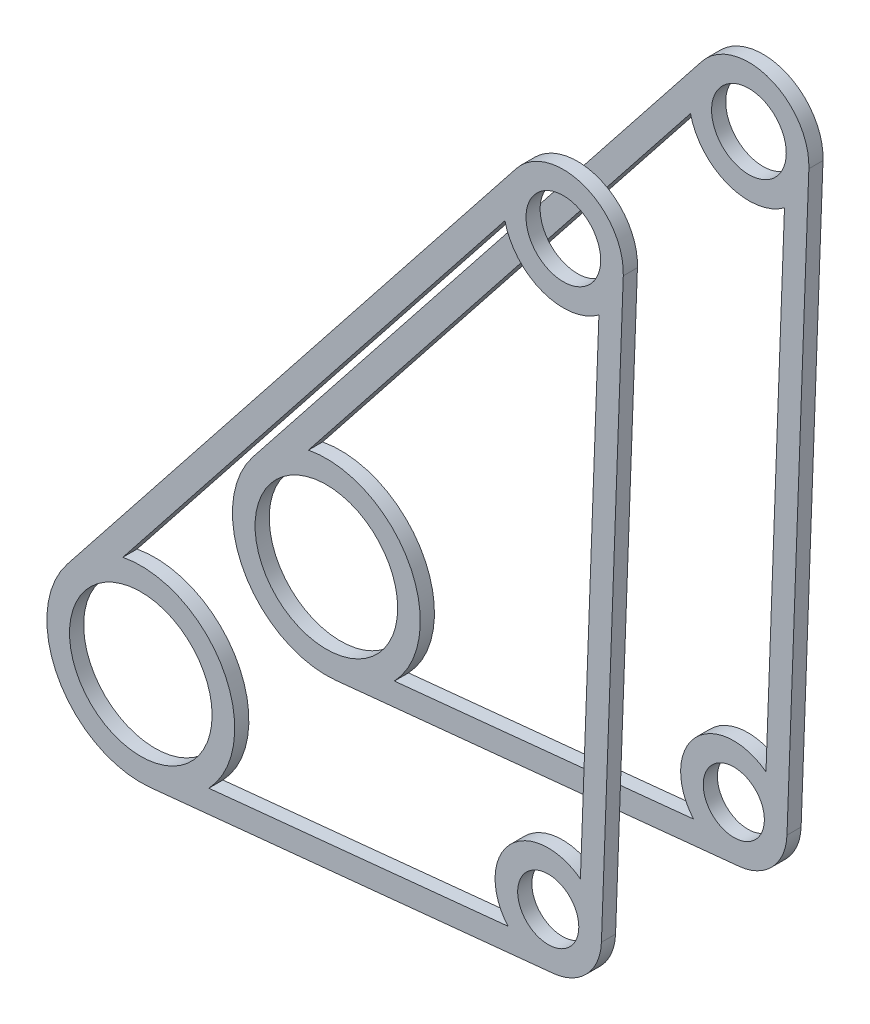
SolidWorks part; units mm, degrees
ref_plane "Front Plane" through (0, 0, 0) normal (0, 0, 1) x (1, 0, 0)
ref_plane "Top Plane" through (0, 0, 0) normal (0, 1, 0) x (1, 0, 0)
ref_plane "Right Plane" through (0, 0, 0) normal (1, 0, 0) x (0, 0, -1)
sketch "Sketch1" plane through (0, 0, 0) normal (0, 0, 1) x (1, 0, 0)
  line L0 (0, 0) -> (45.72, 0) construction
  line L1 (45.72, 0) -> (47.4133, 66.0183) construction
  line L2 (47.4133, 66.0183) -> (0, 0) construction
  line L3 (-8.2641, 6.5435) -> (42.1363, 70.1967)
  line L4 (54.1397, 65.7681) -> (51.6849, -0.2219)
  line L5 (46.3169, -5.9391) -> (1.0541, -10.4882)
  line L6 (-6.2728, 4.9667) -> (44.1276, 68.6199)
  line L7 (0.8001, -7.9609) -> (46.0629, -3.4118)
  line L8 (49.1466, -0.1275) -> (51.6014, 65.8625)
  circle A0 centre (0, 0) radius 8.001
  circle A1 centre (45.72, 0) radius 3.429
  circle A2 centre (47.4133, 66.0183) radius 4.191
  circle A3 centre (0, 0) radius 10.541
  circle A4 centre (45.72, 0) radius 5.969
  circle A5 centre (47.4133, 66.0183) radius 6.731
  dimension "D1" = 8.382
  dimension "D2" = 6.858
  dimension "D3" = 16.002
  dimension "D6" = 2.54
  dimension "D7" = 2.54
  dimension "D8" = 2.54
  dimension "D5" = 66.04
  dimension "2.7" = 45.72
  dimension "D9" = 81.28
extrude "Boss-Extrude1" add sketch "Sketch1" along normal blind 1.5875 from offset 9.6177 contours A5 L3 A3 L6 | L6 A3 A0 | A4 A3 L5 | A4 L8 A1 | A5 L8 A4 L4 | A5 L6 A2 L8 | A3 L6 A0 | L8 A4 A1 | L6 A5 L8 A2 region at (-5.3351, 8.7687, 0) region at (18.2248, 37.9962, 0) region at (49.5658, 72.2042, 0) region at (24.179, -6.9398, 0) region at (6.5454, 7.9412, 0) region at (42.6044, 66.4669, 0) region at (43.5656, -5.4055, 0) region at (51.6669, 32.6998, 0) region at (41.4687, 3.9916, 0)
extrude "Boss-Extrude2" add sketch "Sketch1<4>" against normal blind 1.5875 from offset 9.6177 separate body contours A5 L3 A3 L6 | L6 A3 A0 | A3 L6 A0 | A4 A3 L5 | A4 L8 A1 | L8 A4 A1 | A5 L8 A4 L4 | L6 A5 L8 A2 | A5 L6 A2 L8 region at (-5.3351, 8.7687, 0) region at (18.2248, 37.9962, 0) region at (49.5658, 72.2042, 0) region at (24.179, -6.9398, 0) region at (6.5454, 7.9412, 0) region at (42.6044, 66.4669, 0) region at (43.5656, -5.4055, 0) region at (51.6669, 32.6998, 0) region at (41.4687, 3.9916, 0) offset against normal yes
sketch "Sketch1<4>" plane through (0, 0, 0) normal (0, 0, 1) x (1, 0, 0) same geometry as "Sketch1"
equation "\"D19@Boss-Extrude2\"=\"Gap\"/2"
equation "\"Gap\"= .8198 - 1 / 16"
equation "\"D19@Boss-Extrude1\"=\"Gap\"/2"
